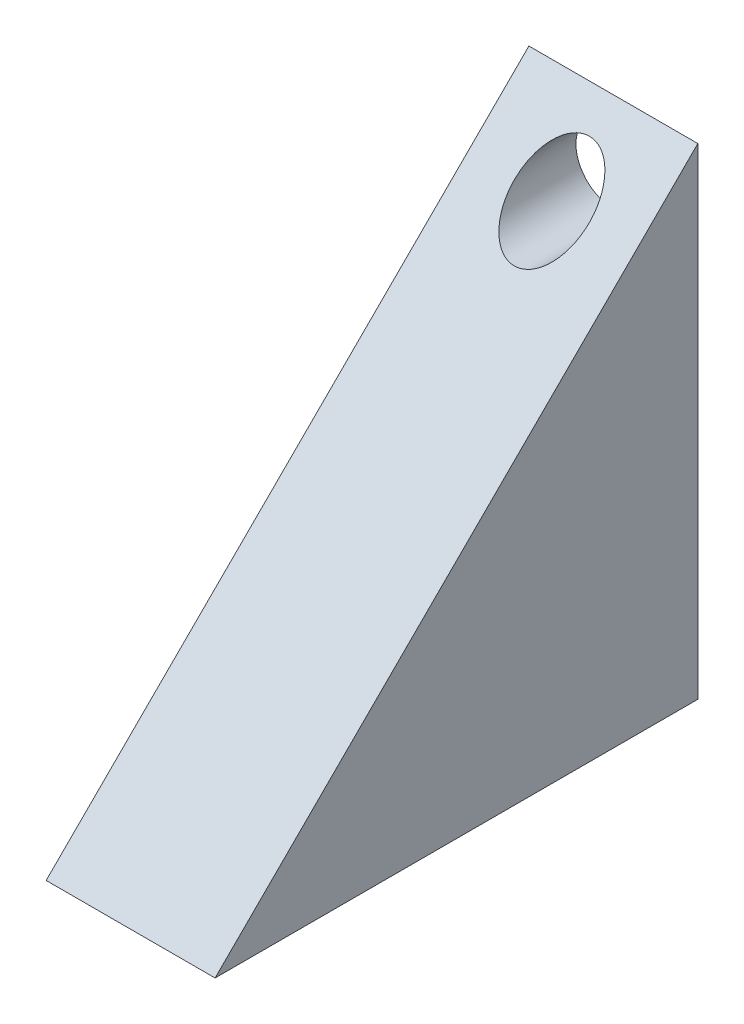
SolidWorks part; units mm, degrees
ref_plane "Front Plane" through (0, 0, 0) normal (0, 0, 1) x (1, 0, 0)
ref_plane "Top Plane" through (0, 0, 0) normal (0, 1, 0) x (1, 0, 0)
ref_plane "Right Plane" through (0, 0, 0) normal (1, 0, 0) x (0, 0, -1)
sketch "Sketch2" plane through (0, 0, 0) normal (1, 0, 0) x (0, 0, -1)
  line L0 (-4.1438, -6.4516) -> (15.8562, -6.4516)
  line L1 (15.8562, -6.4516) -> (15.8562, 13.4874)
  line L2 (15.8562, 13.4874) -> (-4.1438, -6.4516)
  dimension "D1" = 19.939
  dimension "D2" = 20
extrude "Boss-Extrude2" add sketch "Sketch2" along normal blind 7
sketch "Sketch4" plane through (0, 0, -15.8562) normal (0, 0, -1) x (-1, 0, 0)
  line L0 (0, -6.4516) -> (0, 13.4874) construction
  line L1 (-7, 13.4874) -> (0, 13.4874) construction
  circle A0 centre (-3.5, 10.9474) radius 1.55
  point P4 (0, 0)
  dimension "D1" = 3.5
  dimension "D2" = 2.54
extrude "Cut-Extrude1" cut sketch "Sketch4" against normal through all
